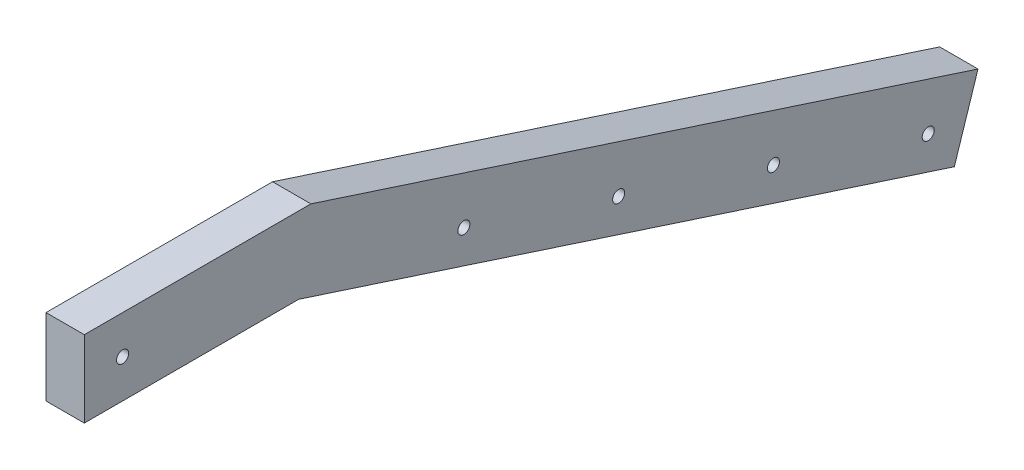
SolidWorks part; units mm, degrees
ref_plane "Front Plane" through (0, 0, 0) normal (0, 0, 1) x (1, 0, 0)
ref_plane "Top Plane" through (0, 0, 0) normal (0, 1, 0) x (1, 0, 0)
ref_plane "Right Plane" through (0, 0, 0) normal (1, 0, 0) x (0, 0, -1)
sketch "Sketch1" plane through (0, 0, 0) normal (1, 0, 0) x (0, 0, -1)
  line L8 (0, 0) -> (-150.2859, 0)
  line L9 (-150.2859, 0) -> (-150.2859, -50.8)
  line L10 (-150.2859, -50.8) -> (-8.0459, -50.8)
  line L11 (-8.0459, -50.8) -> (426.7771, -192.0826)
  line L12 (0, 0) -> (442.4752, -143.7689)
  line L13 (442.4752, -143.7689) -> (426.7771, -192.0826)
  dimension "D1" = 50.8
  dimension "D2" = 50.8
  dimension "D3" = 142.24
  dimension "D4" = 457.2
  dimension "D5" = 198
extrude "Boss-Extrude1" add sketch "Sketch1" along normal blind 25.4 contours L8 L9 L10 L11 L13 L12
sketch "Sketch2" plane through (0, 0, 0) normal (-1, 0, 0) x (0, 0, 1)
  line L0 (150.2859, -25.4) -> (-95.6238, -25.4) construction
  line L1 (150.2859, 0) -> (150.2859, -50.8) construction
  line L2 (-434.6261, -167.9257) -> (76.3227, -97.1997) construction
  line L3 (-442.4752, -143.7689) -> (-426.7771, -192.0826) construction
  circle A0 centre (124.8859, -25.4) radius 4
  circle A1 centre (-409.466, -164.443) radius 4
  dimension "D1" = 8
  dimension "D3" = 8
  dimension "D2" = 25.4
  dimension "D4" = 25.4
extrude "Cut-Extrude1" cut sketch "Sketch2" against normal through all
pattern_linear "LPattern1" count 1 spacing 107.95 rebuild error yes
pattern_linear "LPattern2" count 4 spacing 107.95 along (0, 0.309, 0.9511) of face at (25.4, -164.443, -405.466)
equation "\"w\"= 2"
equation "\"l2\"= 18"
equation "\"l1\"= 5.6"
equation "\"D1@Sketch1\"=\"w\""
equation "\"D2@Sketch1\"=\"2\""
equation "\"D3@Sketch1\"=\"l1\""
equation "\"D4@Sketch1\"=\"l2\""
equation "\"a\"= 53 - 35 + 180"
equation "\"D5@Sketch1\"=\"a\""
equation "\"D1@LPattern1\"=(\"l1\"/4.25)"
equation "\"D1@LPattern2\"=\"l2\"/4.25"
